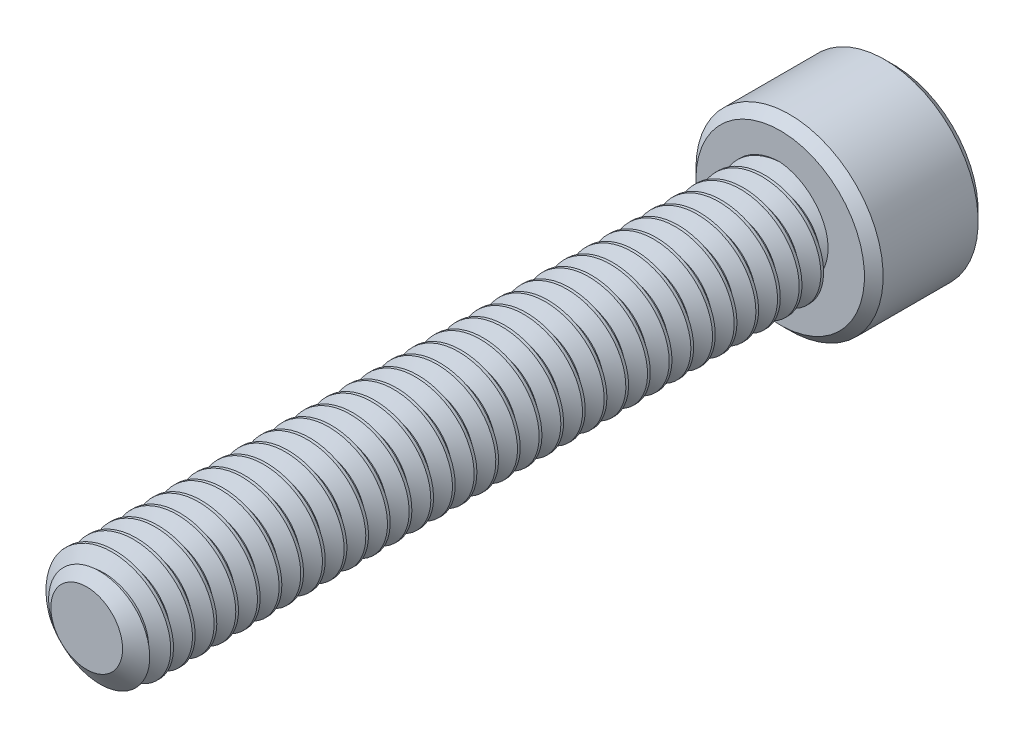
SolidWorks part; units mm, degrees
other "DetailItem1"
ref_plane "Front Plane" through (0, 0, 0) normal (0, 0, 1) x (1, 0, 0)
ref_plane "Top Plane" through (0, 0, 0) normal (0, 1, 0) x (1, 0, 0)
ref_plane "Right Plane" through (0, 0, 0) normal (1, 0, 0) x (0, 0, -1)
sketch "Sketch1" plane through (0, 0, 0) normal (0, 0, 1) x (1, 0, 0)
  circle A0 centre (0, 0) radius 2.0828
  dimension "OD" = 4.1656
extrude "Extrude1" add sketch "Sketch1" against normal blind 25.4
sketch "Sketch2" plane through (0, 0, 0) normal (0, 0, 1) x (1, 0, 0)
  circle A0 centre (0, 0) radius 2.0828 construction
  circle A1 centre (0, 0) radius 2.0828
curve "Helix/Spiral1" pitch 0.7937 height 26.1937 turns 33 parameters "pitch"=0.7937
sketch "Sketch3" plane through (0, 0, 0) normal (1, 0, 0) x (0, 0, -1)
  line L0 (-0.6945, 2.0828) -> (-0.3969, 1.5672)
  line L1 (-0.3969, 1.5672) -> (-0.2977, 1.5672)
  line L2 (-0.2977, 1.5672) -> (0, 2.0828)
  line L3 (-0.6945, 2.0828) -> (0, 2.0828)
  line L4 (-0.3473, 2.0828) -> (-0.3473, 1.5672) construction
  line L5 (-0.5457, 1.825) -> (-0.1488, 1.825) construction
  line L6 (0, 2.0828) -> (0, -2.0828) construction
  dimension "D1" = 0.0992
  dimension "D2" = 0.3969
  dimension "D3" = 60
sweep "Cut-Sweep1" cut profiles "Sketch3" path "Helix/Spiral1"
sketch "Sketch4" plane through (0, 0, 0) normal (1, 0, 0) x (0, 0, -1)
  line L0 (0.5388, 2.0828) -> (0, 1.3132)
  line L1 (0, 1.3132) -> (0, 2.0828)
  line L2 (0.5388, 2.0828) -> (0, 2.0828)
  line L3 (-0.6945, 2.0828) -> (0, 2.0828) construction
  line L4 (0, 0) -> (7.0209, 0) construction
  dimension "D1" = 55
  dimension "D2" = 0.254
revolve "Cut-Revolve1" cut sketch "Sketch4" angle 360 about L4
sketch "Sketch5" plane through (0, 0, 0) normal (1, 0, 0) x (0, 0, -1)
  line L0 (25.4, -1.5805) -> (25.4, 1.4861) construction
  line L1 (25.4, 2.2098) -> (0.1202, 2.2098)
  line L2 (25.4, 2.2098) -> (25.4, 0)
  line L3 (25.4, 0) -> (0, 0)
  line L4 (0, 1.8796) -> (0, 0)
  line L5 (0.1202, 2.2098) -> (0, 1.8796)
  line L6 (0, 0) -> (9.9695, 0) construction
  point P3 (0, 2.2098)
  point P10 (0, 2.2098)
  dimension "D1" = 0.3302
  dimension "D2" = 0.127
  dimension "D3" = 20
  dimension "Min Thread" = 0
revolve "partially thread" [suppressed] add sketch "Sketch5" angle 360 about L6
sketch "Sketch6" plane through (0, 0, -25.4) normal (0, 0, -1) x (-1, 0, 0)
  circle A0 centre (0, 0) radius 3.429
  dimension "head dia" = 6.858
extrude "Extrude2" add sketch "Sketch6" along normal blind 4.1656
sketch "Sketch7" plane through (0, 0, -29.5656) normal (0, 0, -1) x (-1, 0, 0)
  line L1 (0, 2.0622) -> (-1.7859, 1.0311)
  line L2 (-1.7859, 1.0311) -> (-1.7859, -1.0311)
  line L3 (-1.7859, -1.0311) -> (0, -2.0622)
  line L4 (0, -2.0622) -> (1.7859, -1.0311)
  line L5 (1.7859, -1.0311) -> (1.7859, 1.0311)
  line L6 (1.7859, 1.0311) -> (0, 2.0622)
  circle A0 centre (0, 0) radius 1.7859 construction
  dimension "hex dia" = 3.5719
extrude "Cut-Extrude1" cut sketch "Sketch7" against normal blind 2.6789
sketch "Sketch8" plane through (0, 0, -29.5656) normal (0, 0, -1) x (-1, 0, 0)
  circle A0 centre (0, 0) radius 2.0622
extrude "Cut-Extrude2" cut sketch "Sketch8" against normal through all draft 45
chamfer "Chamfer1" distance 0.3429 angle 45 2 edges at (-3.429, 0, -29.5656) (-3.429, 0, -25.4)
sketch "Sketch9" plane through (0, 0, 0) normal (1, 0, 0) x (0, 0, -1)
  line L0 (0, 2.0828) -> (0, -2.0828) construction
  line L1 (1.9844, 2.0828) -> (1.9844, -2.0828) construction
  dimension "D1" = 1.9844
equation "\"D3@Helix/Spiral1\" = \"screw length@Extrude1\"+\"pitch@Helix/Spiral1\""
equation "\"D1@Sketch3\" = \"pitch@Helix/Spiral1\"*.125"
equation "\"D2@Sketch3\" = \"pitch@Helix/Spiral1\"*.5"
equation "\"D1@Cut-Extrude1\" = \"hex dia@Sketch7\"*.75"
equation "\"D1@Chamfer1\" = \"head dia@Sketch6\"*.05"
equation "\"D1@Sketch9\" = \"pitch@Helix/Spiral1\"*2.5"
